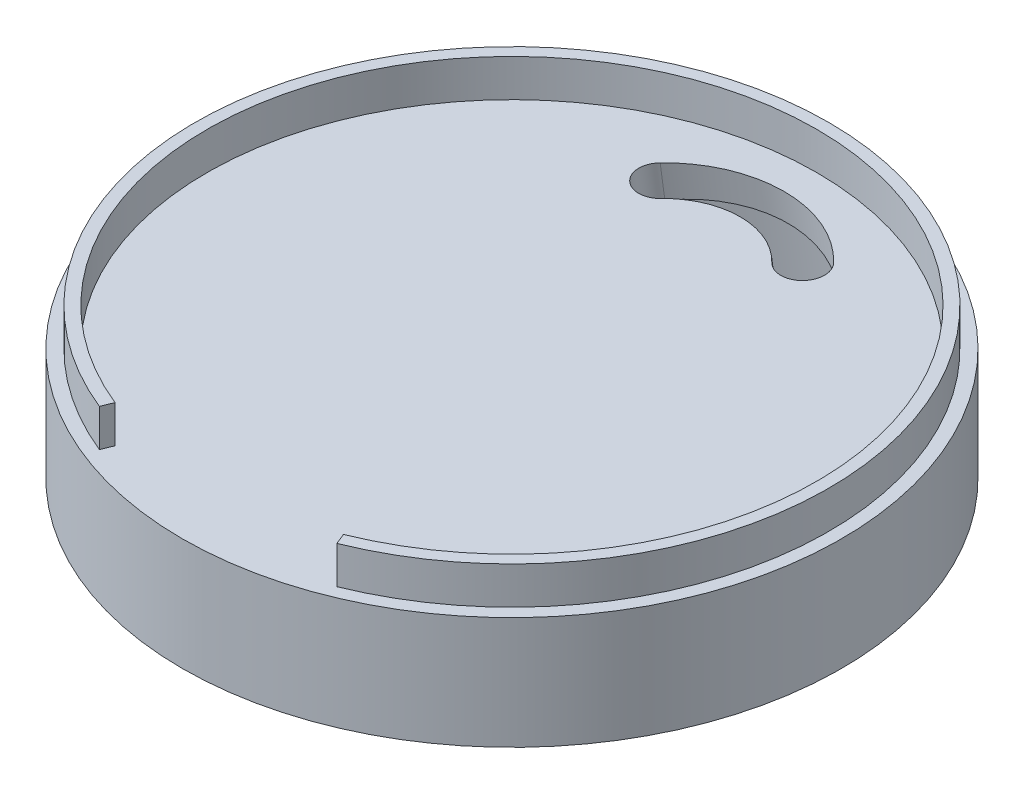
SolidWorks part; units mm, degrees
ref_plane "Front Plane" through (0, 0, 0) normal (0, 0, 1) x (1, 0, 0)
ref_plane "Top Plane" through (0, 0, 0) normal (0, 1, 0) x (1, 0, 0)
ref_plane "Right Plane" through (0, 0, 0) normal (1, 0, 0) x (0, 0, -1)
sketch "Sketch1" plane through (0, 0, 0) normal (0, 1, 0) x (1, 0, 0)
  circle A0 centre (0, 0) radius 44
  dimension "D1" = 88
extrude "Boss-Extrude1" add sketch "Sketch1" along normal blind 15 contours A0
sketch "Sketch2" plane through (0, 15, 0) normal (0, 1, 0) x (1, 0, 0)
  line L0 (0, 0) -> (15.8459, -39.2199) construction
  line L1 (0, 0) -> (-15.8459, -39.2199) construction
  line L2 (15.2465, -37.7364) -> (15.8459, -39.2199)
  line L3 (-15.2465, -37.7364) -> (-15.8459, -39.2199)
  line L5 (0, 0) -> (0, -44) construction
  line L6 (0, -8.25) -> (0, 8.25) construction
  arc A0 (15.2465, -37.7364) -> (-15.2465, -37.7364) centre (0, 0) ccw
  arc A1 (15.8459, -39.2199) -> (-15.8459, -39.2199) centre (0, 0) ccw
  circle A2 centre (0, 0) radius 44 construction
  dimension "D1" = 81.4
  dimension "D2" = 84.6
  dimension "D3" = 44
  dimension "D4" = 22
extrude "Boss-Extrude2" add sketch "Sketch2" along normal blind 5
sketch "Sketch3" plane through (0, 0, 0) normal (0, -1, 0) x (1, 0, 0)
  line L0 (0, 0) -> (0, 44) construction
  line L1 (15.2465, 37.7364) -> (15.8459, 39.2199) construction
  line L2 (-15.8459, 39.2199) -> (-15.2465, 37.7364) construction
  circle A1 centre (0, 0) radius 44 construction
sketch "Sketch4" plane through (0, 0, 0) normal (1, 0, 0) x (0, 0, -1)
  line L0 (-44, 0) -> (44, 12) construction
  line L1 (44, 0) -> (44, 15) construction
  line L2 (44, 15) -> (-44, 15) construction
  line L3 (0, 6) -> (9.4986, -63.6565) construction
  dimension "D1" = 3
ref_plane "Plane1" through (0, 5.8905, 0.8032) normal (0, -0.9908, -0.1351) x (-1, 0, 0)
sketch "Sketch5" plane through (0, 5.8905, 0.8032) normal (0, -0.9908, -0.1351) x (-1, 0, 0)
  circle A0 centre (0, 0) radius 40
  dimension "D1" = 80
extrude "Cut-Extrude1" cut sketch "Sketch5" along normal blind 20
sketch "Sketch6" plane through (0, 5.8905, 0.8032) normal (0, -0.9908, -0.1351) x (1, 0, 0)
  line L0 (0, 0) -> (0, -51.1786) construction
  line L1 (0, -8.25) -> (0, 8.25) construction
  arc A0 (-9.488, -31.0918) -> (9.488, -31.0918) centre (0, -21.9556) ccw construction
  arc A1 (-11.5811, -33.1074) -> (11.5811, -33.1074) centre (0, -21.9556) ccw
  arc A2 (-7.3949, -29.0763) -> (7.3949, -29.0763) centre (0, -21.9556) ccw
  arc A3 (-7.3949, -29.0763) -> (-11.5811, -33.1074) centre (-9.488, -31.0918) ccw
  arc A4 (11.5811, -33.1074) -> (7.3949, -29.0763) centre (9.488, -31.0918) ccw
  point P6 (0, -35.1273)
extrude "Cut-Extrude2" cut sketch "Sketch6" against normal blind 10
sketch "Sketch7" plane through (0, 6.0825, -0.6052) normal (0, 0.9908, 0.1351) x (1, 0, 0)
  line L0 (0, -1.4215) -> (0, -44.3855) construction
  line L1 (0, -9.6715) -> (0, 6.8285) construction
  circle A0 centre (14.3708, -14.4215) radius 3
  circle A1 centre (-14.3708, -14.4215) radius 3
  dimension "D1" = 6
  dimension "D2" = 13
extrude "Cut-Extrude3" cut sketch "Sketch7" along normal blind 3 contours A0 | A1
fillet "Fillet4" radius 1 1 edges at (0, 11.295, -38.83)
sketch "Sketch8" plane through (0, 5.8905, 0.8032) normal (0, -0.9908, -0.1351) x (-1, 0, 0)
  line L0 (5.2504, 0) -> (-5.2504, 0) construction
  line L1 (5.2504, 0) -> (-5.2504, 0)
  arc A0 (-5.2504, 0) -> (5.2504, 0) centre (0, 0) ccw
ref_plane "Plane2" through (0, 0, 0) normal (0, 0.1351, -0.9908) x (1, 0, 0)
sketch "Sketch9" plane through (0, 0, 0) normal (0, 0.1351, -0.9908) x (1, 0, 0)
  line L0 (-5.2504, -5.945) -> (5.2504, -5.945) construction
  line L5 (0, 4.055) -> (0, -5.945)
  line L6 (0, -5.945) -> (4.4721, -5.945)
  line L9 (0, -5.945) -> (0, 64.3562) construction
  arc A0 (4.4721, -5.945) -> (0, 4.055) centre (0, -1.945) ccw
  dimension "D1" = 12
  dimension "D2" = 4
revolve "Revolve4" add sketch "Sketch9" angle 360 about L5
